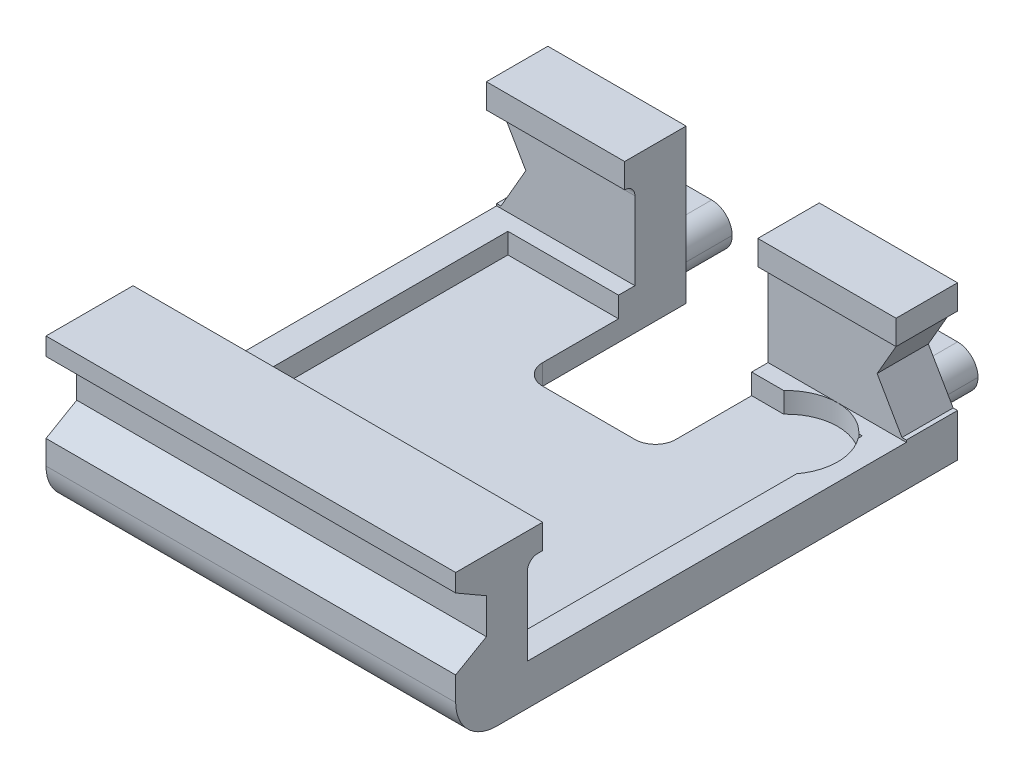
SolidWorks part; units mm, degrees
ref_plane "Front Plane" through (0, 0, 0) normal (0, 0, 1) x (1, 0, 0)
ref_plane "Top Plane" through (0, 0, 0) normal (0, 1, 0) x (1, 0, 0)
ref_plane "Right Plane" through (0, 0, 0) normal (1, 0, 0) x (0, 0, -1)
sketch "Sketch1" plane through (0, 0, 0) normal (0, 1, 0) x (1, 0, 0)
  line L0 (0, 11.5) -> (0, -11.5) construction
  line L1 (10, 11.5) -> (-10, 11.5)
  line L2 (10, 11.5) -> (10, -11.5)
  line L3 (10, -11.5) -> (-10, -11.5)
  line L4 (-10, 11.5) -> (-10, -11.5)
  line L5 (10, 11.5) -> (-10, -11.5) construction
  line L6 (10, -11.5) -> (-10, 11.5) construction
  line L21 (-3.25, 3.5) -> (3.25, 3.5)
  line L29 (-3.25, 3.5) -> (-3.25, 11.5)
  line L30 (-3.25, 11.5) -> (3.25, 11.5)
  line L31 (3.25, 3.5) -> (3.25, 11.5)
  line L32 (-3.25, 3.5) -> (3.25, 11.5) construction
  line L33 (-3.25, 11.5) -> (3.25, 3.5) construction
  line L41 (-6, 14.5) -> (-6, 11.5) construction
  line L42 (-4, 11.5) -> (-8, 11.5)
  line L43 (-4, 11.5) -> (-4, 14.5)
  line L44 (-4, 14.5) -> (-8, 14.5)
  line L45 (-8, 11.5) -> (-8, 14.5)
  line L46 (4, 11.5) -> (8, 11.5)
  line L47 (8, 11.5) -> (8, 14.5)
  line L48 (4, 14.5) -> (8, 14.5)
  line L49 (4, 11.5) -> (4, 14.5)
  point P0 (0, 0)
  point P14 (0, 7.5)
  dimension "D1" = 20
  dimension "D2" = 23
  dimension "D3" = 4
  dimension "D6" = 6.5
  dimension "D7" = 8
  dimension "D8" = 12
  dimension "D9" = 3
extrude "Boss-Extrude1" add sketch "Sketch1" along normal blind 2
fillet "Fillet1" radius 1 10 edges at (-3.25, 1, -3.5) (3.25, 1, -3.5) (-8, 0, -13) (-8, 2, -13) (4, 0, -13) (4, 2, -13) (8, 0, -13) (8, 2, -13) (-4, 0, -13) (-4, 2, -13)
sketch "Sketch4" plane through (0, 2, 0) normal (0, 1, 0) x (1, 0, 0)
  line L0 (0, 5.3573) -> (0, -4.2859) construction
  line L2 (-8.65, 8.2) -> (8.65, 8.2)
  line L3 (-8.65, 8.2) -> (-8.65, -9.5)
  line L4 (-8.65, -9.5) -> (8.65, -9.5)
  line L5 (8.65, 8.2) -> (8.65, -9.5)
  line L6 (-8.65, 8.2) -> (8.65, -9.5) construction
  line L7 (-8.65, -9.5) -> (8.65, 8.2) construction
  line L11 (10, -11.5) -> (-10, -11.5) construction
  point P1 (0, -0.65)
  dimension "D1" = 17.3
  dimension "D2" = 2
  dimension "D3" = 17.7
extrude "Cut-Extrude3" cut sketch "Sketch4" against normal blind 1
sketch "Sketch5" plane through (10, 0, 0) normal (1, 0, 0) x (0, 0, -1)
  line L0 (8.2, 1) -> (-9.5, 1) construction
  line L1 (8.2, 1) -> (-9.5, 1)
  line L2 (11.5, 2) -> (-11.5, 2) construction
  line L3 (-11.5, 2) -> (-9.5, 2)
  line L4 (-11.5, 2) -> (-11.5, 6.3)
  line L5 (-11.5, 6.3) -> (-9.5, 6.3)
  line L6 (-9.5, 2) -> (-9.5, 6.3)
  line L7 (11.5, 2) -> (9, 2)
  line L8 (11.5, 2) -> (11.5, 6.3)
  line L9 (11.5, 6.3) -> (9, 6.3)
  line L10 (9, 2) -> (9, 6.3)
  line L11 (-11.5, 6.3) -> (-8.75, 6.3)
  line L12 (-11.5, 6.3) -> (-11.5, 7.5)
  line L13 (-11.5, 7.5) -> (-8.75, 7.5)
  line L14 (-8.75, 6.3) -> (-8.75, 7.5)
  line L15 (11.5, 6.3) -> (8.5, 6.3)
  line L16 (11.5, 6.3) -> (11.5, 7.5)
  line L17 (11.5, 7.5) -> (8.5, 7.5)
  line L18 (8.5, 6.3) -> (8.5, 7.5)
  line L19 (-11.5, 2) -> (-11.5, 0) construction
  line L20 (11.5, 2) -> (11.5, 0) construction
  dimension "D1" = 2
  dimension "D2" = 5.3
  dimension "D3" = 18.5
  dimension "D4" = 1.2
  dimension "D5" = 0.75
  dimension "D6" = 0.5
extrude "Boss-Extrude3" add sketch "Sketch5" against normal up to surface (20 mm away) up to face at (-10, 1, 0)
sketch "Sketch7" plane through (0, 7.5, 0) normal (0, 1, 0) x (1, 0, 0)
  line L1 (-3.25, 11.5) -> (3.25, 11.5)
  line L2 (-3.25, 11.5) -> (-3.25, 8.5)
  line L3 (-3.25, 8.5) -> (3.25, 8.5)
  line L4 (3.25, 11.5) -> (3.25, 8.5)
  line L5 (-10, 8.5) -> (10, 8.5) construction
  line L11 (0, 5.6258) -> (0, -4.3103) construction
  line L16 (3.25, 4.5) -> (3.25, 8.2) construction
  line L17 (-10, 8.5) -> (10, 8.5) construction
extrude "Cut-Extrude5" cut sketch "Sketch7" against normal up to next
sketch "Sketch8" plane through (0, 0, -11.5) normal (0, 0, -1) x (-1, 0, 0)
  line L0 (-3.25, 7.5) -> (-10, 7.5) construction
  line L1 (-8.5751, 4.2) -> (-9.7876, 6.3)
  line L2 (-9.7876, 6.3) -> (-12.2124, 6.3)
  line L3 (-12.2124, 6.3) -> (-13.4249, 4.2)
  line L4 (-13.4249, 4.2) -> (-12.2124, 2.1)
  line L5 (-12.2124, 2.1) -> (-9.7876, 2.1)
  line L6 (-9.7876, 2.1) -> (-8.5751, 4.2)
  line L7 (0, 12.0608) -> (0, -4.099) construction
  line L8 (12.2124, 2.1) -> (9.7876, 2.1)
  line L9 (13.4249, 4.2) -> (12.2124, 2.1)
  line L10 (12.2124, 6.3) -> (13.4249, 4.2)
  line L11 (9.7876, 6.3) -> (12.2124, 6.3)
  line L12 (8.5751, 4.2) -> (9.7876, 6.3)
  line L13 (9.7876, 2.1) -> (8.5751, 4.2)
  circle A0 centre (-11, 4.2) radius 2.1 construction
  dimension "D1" = 3.3
  dimension "D2" = 22
  dimension "D3" = 4.2
extrude "Cut-Extrude6" cut sketch "Sketch8" against normal blind 3.5
fillet "Fillet3" radius 0.5 2 edges at (6.5188, 6.3, -9) (0, 6.3, 9.5)
sketch "Sketch9" plane through (10, 0, 0) normal (1, 0, 0) x (0, 0, -1)
  line L0 (-11.5, 7.5) -> (-11.5, 0) construction
  line L1 (-11.5, 4.034) -> (-11.5, 5.766)
  line L2 (-11.5, 5.766) -> (-13, 6.6321)
  line L3 (-13, 6.6321) -> (-14.5, 5.766)
  line L4 (-14.5, 5.766) -> (-14.5, 4.034)
  line L5 (-14.5, 4.034) -> (-13, 3.1679)
  line L6 (-13, 3.1679) -> (-11.5, 4.034)
  line L7 (-11.5, 7.5) -> (-8.75, 7.5) construction
  line L8 (-13, 6.6321) -> (-13, 7.5)
  line L9 (-13, 7.5) -> (-11.5, 7.5)
  line L10 (-13, 3.1679) -> (-13, 0)
  line L11 (-13, 0) -> (-11.5, 0)
  circle A0 centre (-13, 4.9) radius 1.5 construction
  line M11 (-11.5, 7.5) -> (-11.5, 0)
  dimension "D1" = 3
  dimension "D2" = 2.6
extrude "Boss-Extrude4" add sketch "Sketch9" against normal up to surface (20 mm away) contours L9 L8 L2 M11 | L10 L11 L6 M11 up to face at (-10, 3.7912, 2.5094)
sketch "Sketch10" plane through (0, 2, 0) normal (0, 1, 0) x (1, 0, 0)
  line L2 (10, 9) -> (3.25, 9) construction
  line L3 (8.65, -9.5) -> (8.65, 8.2) construction
  circle A0 centre (6.65, 6.5) radius 2.5
  point P6 (9.15, 6.5)
  dimension "D2" = 5
  dimension "D1" = 0.5
extrude "Cut-Extrude7" cut sketch "Sketch10" against normal up to surface (1 mm away) up to face at (0, 1, -2.9386)
fillet "Fillet4" radius 2 1 edges at (0, 0, 13)
